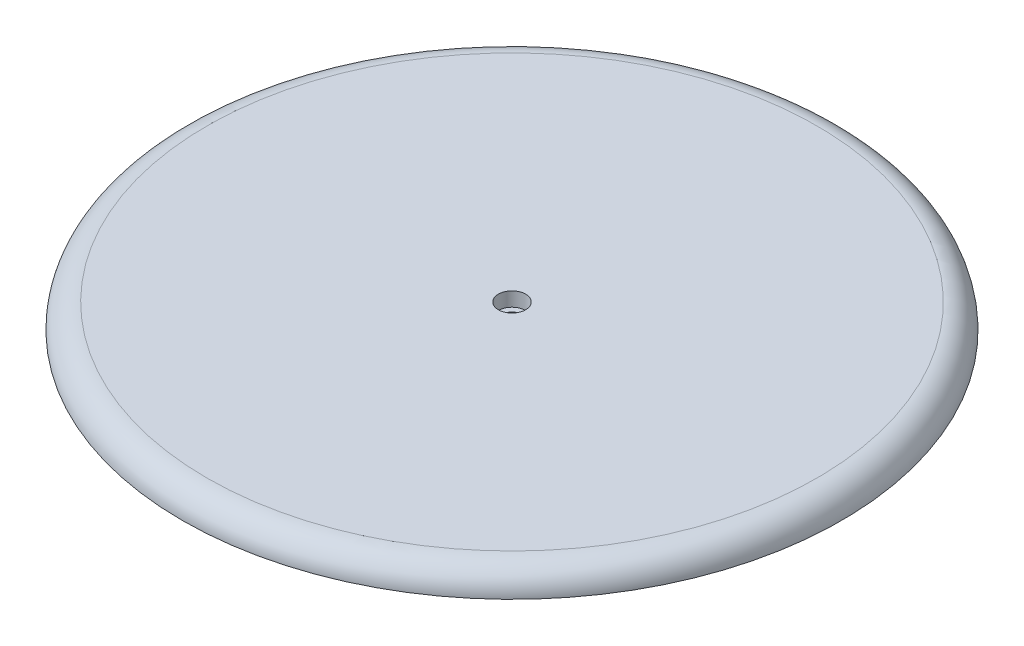
SolidWorks part; units mm, degrees
ref_plane "Front Plane" through (0, 0, 0) normal (0, 0, 1) x (1, 0, 0)
ref_plane "Top Plane" through (0, 0, 0) normal (0, 1, 0) x (1, 0, 0)
ref_plane "Right Plane" through (0, 0, 0) normal (1, 0, 0) x (0, 0, -1)
sketch "Sketch1" plane through (0, 0, 0) normal (0, 1, 0) x (1, 0, 0)
  circle A0 centre (0, 0) radius 57.15
  circle A1 centre (0, 0) radius 67.15
  dimension "D1" = 114.3
  dimension "D2" = 10
extrude "Boss-Extrude1" add sketch "Sketch1" along normal blind 5 contours A1
extrude "Boss-Extrude2" add sketch "Sketch1<3>" against normal blind 2 contours A0
sketch "Sketch1<3>" plane through (0, 0, 0) normal (0, 1, 0) x (1, 0, 0) same geometry as "Sketch1"
sketch "Sketch2" plane through (0, 5, 0) normal (0, 1, 0) x (1, 0, 0)
  circle A0 centre (0, 0) radius 2.775
  dimension "D1" = 5.55
extrude "Cut-Extrude1" cut sketch "Sketch2" against normal blind 2.89
sketch "Sketch3" plane through (0, 2.11, 0) normal (0, 1, 0) x (1, 0, 0)
  circle A0 centre (0, 0) radius 1.6
  dimension "D1" = 3.2
extrude "Cut-Extrude2" cut sketch "Sketch3" against normal up to next
fillet "Fillet1" radius 5 1 edges at (0, 5, 67.15)
